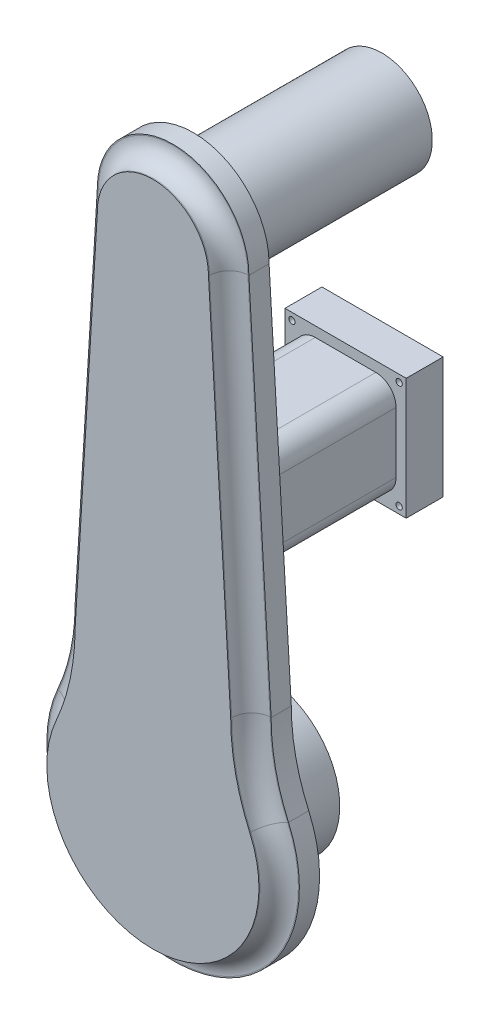
SolidWorks part; units mm, degrees
ref_plane "前视基准面" through (0, 0, 0) normal (0, 0, 1) x (1, 0, 0)
ref_plane "上视基准面" through (0, 0, 0) normal (0, 1, 0) x (1, 0, 0)
ref_plane "右视基准面" through (0, 0, 0) normal (1, 0, 0) x (0, 0, -1)
other "Configuration Table"
sketch "草图1" plane through (0, 0, 0) normal (0, 0, 1) x (1, 0, 0)
  circle A0 centre (-126.8709, 79.3663) radius 75
  circle A1 centre (-126.8709, 579.3663) radius 50
  dimension "D1" = 100
  dimension "D2" = 150
  dimension "D3" = 500
extrude "凸台-拉伸1" add sketch "草图1" along normal mid plane 180
sketch "草图3" plane through (0, 0, 90) normal (0, 0, 1) x (1, 0, 0)
  line L0 (-51.8709, 579.3663) -> (-29.8759, 211.3463)
  line L1 (-126.8709, -270.1227) -> (-126.8709, 939.7643) construction
  line L2 (-201.8709, 579.3663) -> (-223.8658, 211.3463)
  arc A0 (-29.8759, 211.3463) -> (-12.6422, 130.1287) centre (170.1191, 211.3463) ccw
  circle A1 centre (-126.8709, 79.3663) radius 75 construction
  arc A2 (-241.0995, 130.1287) -> (-12.6422, 130.1287) centre (-126.8709, 79.3663) ccw
  arc A3 (-51.8709, 579.3663) -> (-201.8709, 579.3663) centre (-126.8709, 579.3663) ccw
  arc A4 (-223.8658, 211.3463) -> (-241.0995, 130.1287) centre (-423.8609, 211.3463) cw
  point P19 (-12.6422, 130.1287)
  point P20 (-12.6422, 130.1287)
  point P48 (-12.6422, 130.1287)
  dimension "D1" = 296.99
  dimension "D3" = 250
  dimension "D4" = 150
  dimension "D2" = 131.98
extrude "凸台-拉伸2" add sketch "草图3" along normal mid plane 20 contours L0 A0 A2 A4 L2 A3
sketch "草图4" plane through (0, 0, 100) normal (0, 0, 1) x (1, 0, 0)
  line L4 (-181.8681, 578.8154) -> (-203.8667, 210.735)
  line L5 (-49.8751, 210.735) -> (-71.8736, 578.8154)
  line L6 (-181.8681, 578.8154) -> (-203.8667, 210.735)
  line L7 (-49.8751, 210.735) -> (-71.8736, 578.8154)
  arc A8 (-71.8736, 578.8154) -> (-181.8681, 578.8154) centre (-126.8709, 579.3663) ccw
  arc A9 (-222.8229, 122.0067) -> (-203.8667, 210.735) centre (-423.8609, 211.3463) ccw
  arc A10 (-222.8229, 122.0067) -> (-30.9188, 122.0067) centre (-126.8709, 79.3663) ccw
  arc A11 (-49.8751, 210.735) -> (-30.9188, 122.0067) centre (170.1191, 211.3463) ccw
  arc A12 (-71.8736, 578.8154) -> (-181.8681, 578.8154) centre (-126.8709, 579.3663) ccw
  arc A13 (-222.8229, 122.0067) -> (-203.8667, 210.735) centre (-423.8609, 211.3463) ccw
  arc A14 (-222.8229, 122.0067) -> (-30.9188, 122.0067) centre (-126.8709, 79.3663) ccw
  arc A15 (-49.8751, 210.735) -> (-30.9188, 122.0067) centre (170.1191, 211.3463) ccw
  dimension "D1" = 20
extrude "凸台-拉伸3" add sketch "草图4" along normal blind 20 contours A12 L6 A13 A14 A15 L7
fillet "圆角1" radius 19 6 edges at (-126.8709, 634.3663, 100) (-60.8743, 394.7752, 100) (-45.0208, 165.383, 100) (-192.8674, 394.7752, 100) (-208.7209, 165.383, 100) (-126.8709, -25.6337, 100)
mirror "镜向1" about plane through (0, 0, 0) normal (0, 0, 1) of "圆角1", "凸台-拉伸3", "凸台-拉伸2"
sketch "草图5" plane through (0, 0, -80) normal (0, 0, 1) x (1, 0, 0)
  line L1 (-186.1595, 399.0758) -> (-66.1595, 399.0758)
  line L2 (-186.1595, 399.0758) -> (-186.1595, 279.0758)
  line L3 (-186.1595, 279.0758) -> (-66.1595, 279.0758)
  line L4 (-66.1595, 399.0758) -> (-66.1595, 279.0758)
  line L5 (-126.1595, 279.0758) -> (-126.1595, 399.0758) construction
  line L6 (-186.1595, 339.0758) -> (-66.1595, 339.0758) construction
  point P0 (-126.1595, 339.0758)
  dimension "D1" = 120
  dimension "D2" = 120
extrude "凸台-拉伸4" add sketch "草图5" along normal blind 10
mirror "镜向2" about plane through (0, 0, 0) normal (0, 0, 1) of bodies 113
sketch "草图6" plane through (0, 0, -70) normal (0, 0, 1) x (1, 0, 0)
  line L8 (-76.1595, 289.0758) -> (-76.1595, 389.0758)
  line L9 (-76.1595, 389.0758) -> (-176.1595, 389.0758)
  line L10 (-176.1595, 389.0758) -> (-176.1595, 289.0758)
  line L11 (-176.1595, 289.0758) -> (-76.1595, 289.0758)
  line L12 (-76.1595, 289.0758) -> (-76.1595, 389.0758)
  line L13 (-76.1595, 389.0758) -> (-176.1595, 389.0758)
  line L14 (-176.1595, 389.0758) -> (-176.1595, 289.0758)
  line L15 (-176.1595, 289.0758) -> (-76.1595, 289.0758)
  dimension "D1" = 10
extrude "凸台-拉伸5" add sketch "草图6" along normal up to next
fillet "圆角2" radius 20 4 edges at (-76.1595, 389.0758, 0) (-176.1595, 389.0758, 0) (-76.1595, 289.0758, 0) (-176.1595, 289.0758, 0)
sketch "草图7" plane through (-76.1595, 0, 0) normal (1, 0, 0) x (0, 0, -1)
  line L0 (80, 654.3663) -> (80, -45.6337)
split "分割1" trim tools "草图7" bodies to split 115 resulting bodies 116 117
delete or keep bodies "实体-删除/保留 1" type delete bodies bodies 116
sketch "草图8" plane through (0, 0, -80) normal (0, 0, -1) x (-1, 0, 0)
  line L0 (126.1595, 399.0758) -> (126.1595, 279.0758) construction
  line L1 (66.1595, 399.0758) -> (186.1595, 399.0758) construction
  line L2 (186.1595, 279.0758) -> (66.1595, 279.0758) construction
  line L3 (186.1595, 339.0758) -> (66.1595, 339.0758) construction
  line L4 (186.1595, 399.0758) -> (186.1595, 279.0758) construction
  line L5 (66.1595, 279.0758) -> (66.1595, 399.0758) construction
  line L6 (126.1595, 339.0758) -> (73.1265, 392.1088) construction
  circle A0 centre (126.1595, 339.0758) radius 75 construction
  circle A1 centre (73.1265, 392.1088) radius 3.1
  circle A2 centre (179.1925, 392.1088) radius 3.1
  circle A3 centre (179.1925, 286.0428) radius 3.1
  circle A4 centre (73.1265, 286.0428) radius 3.1
  point P16 (0, 0)
  point P17 (176.8019, 385.8933)
  point P18 (126.1595, 339.0758)
  point P25 (126.1595, 339.0758)
  point P26 (179.1925, 392.1088)
  dimension "D1" = 45
  dimension "D2" = 4
  dimension "D3" = 150
extrude "切除-拉伸1" cut sketch "草图8" against normal blind 20
sketch "草图10" plane through (0, 0, -80) normal (0, 0, -1) x (-1, 0, 0)
  circle A0 centre (126.8709, 79.3663) radius 50
extrude "切除-拉伸2" cut sketch "草图10" against normal blind 100
sketch "草图11" plane through (0, 0, 0) normal (0, 1, 0) x (1, 0, 0)
  line L0 (-126.8709, 215.4352) -> (-126.8709, -55.4356) construction
  line L3 (-146.8709, 54.6265) -> (-106.8709, 54.6265)
  line L4 (-146.8709, 54.6265) -> (-146.8709, -5.3735)
  line L5 (-146.8709, -5.3735) -> (-106.8709, -5.3735)
  line L6 (-106.8709, 54.6265) -> (-106.8709, -5.3735)
  line L7 (-126.8709, -5.3735) -> (-126.8709, 54.6265) construction
  line L8 (-146.8709, 24.6265) -> (-106.8709, 24.6265) construction
  point P0 (-126.8709, 24.6265)
  point P3 (-126.8709, 79.9998)
extrude "切除-拉伸3" cut sketch "草图11" along normal blind 40
sketch "草图12" plane through (0, 0, -80) normal (0, 0, -1) x (-1, 0, 0)
  circle A0 centre (126.8709, 79.3663) radius 75
extrude "切除-拉伸4" cut sketch "草图12" against normal blind 90
sketch "草图13" plane through (0, 0, -80) normal (0, 0, -1) x (-1, 0, 0)
  line L4 (66.1595, 279.0758) -> (186.1595, 279.0758)
  line L5 (186.1595, 279.0758) -> (186.1595, 399.0758)
  line L6 (186.1595, 399.0758) -> (66.1595, 399.0758)
  line L7 (66.1595, 399.0758) -> (66.1595, 279.0758)
  line L8 (66.1595, 279.0758) -> (186.1595, 279.0758)
  line L9 (186.1595, 279.0758) -> (186.1595, 399.0758)
  line L10 (186.1595, 399.0758) -> (66.1595, 399.0758)
  line L11 (66.1595, 399.0758) -> (66.1595, 279.0758)
  circle A0 centre (73.1265, 392.1088) radius 3.1
  circle A1 centre (179.1925, 392.1088) radius 3.1
  circle A2 centre (73.1265, 286.0428) radius 3.1
  circle A3 centre (179.1925, 286.0428) radius 3.1
  dimension "D1" = 0
extrude "凸台-拉伸6" add sketch "草图13" along normal blind 26.6
sketch "草图15" plane through (0, 0, -80) normal (0, 0, -1) x (-1, 0, 0)
  circle A1 centre (126.8709, 579.3663) radius 50
  circle A2 centre (126.8709, 579.3663) radius 50
  dimension "D1" = 0
extrude "凸台-拉伸7" add sketch "草图15" along normal blind 26.6
